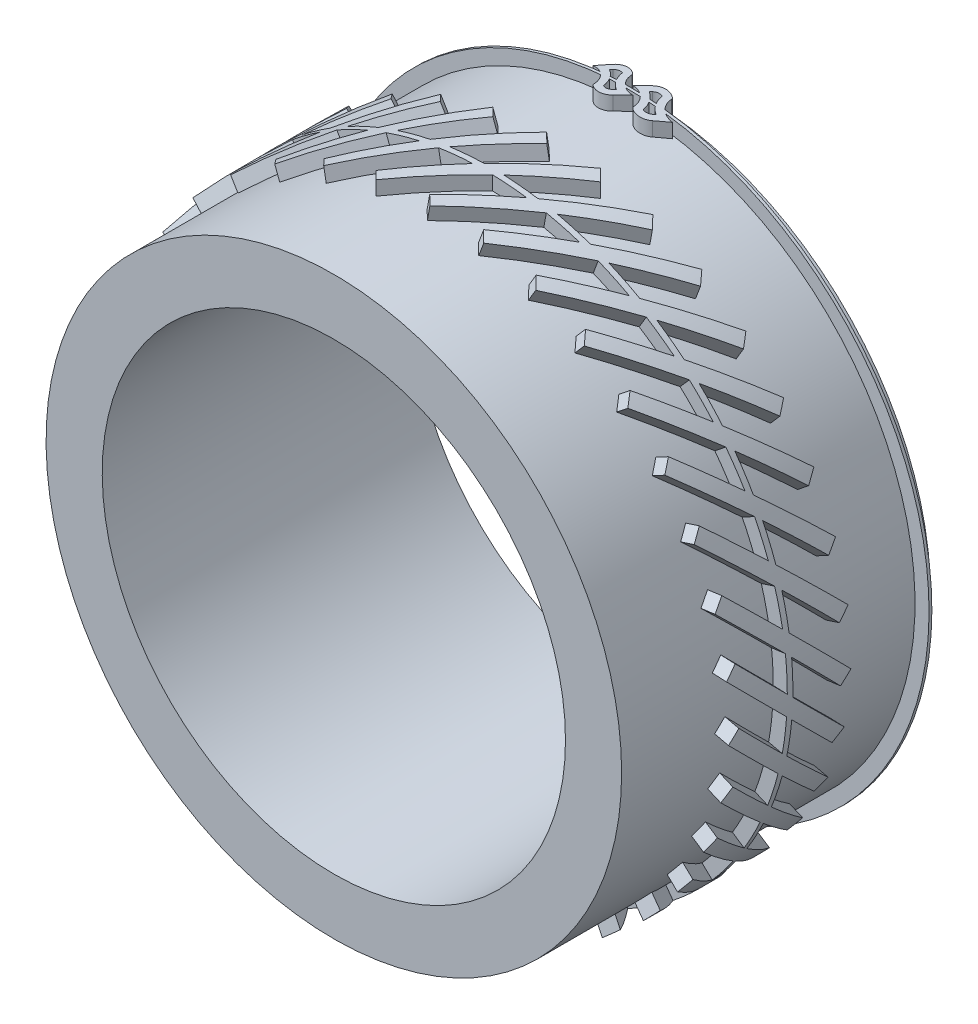
SolidWorks part; units mm, degrees
note: The reader was unsure of these and kept them because the rebuilt part matched: shared geometry of "Sketch1<4>", "Sketch1<5>", "Sketch4<9>".
ref_plane "Front Plane" through (0, 0, 0) normal (0, 0, 1) x (1, 0, 0)
ref_plane "Top Plane" through (0, 0, 0) normal (0, 1, 0) x (1, 0, 0)
ref_plane "Right Plane" through (0, 0, 0) normal (1, 0, 0) x (0, 0, -1)
sketch "Sketch1" plane through (0, 0, 0) normal (0, 0, 1) x (1, 0, 0)
  circle A0 centre (0, 0) radius 10.4775
  circle A1 centre (0, 0) radius 13.6525
  circle A2 centre (0, 0) radius 13.0175
  dimension "D1" = 20.955
  dimension "D2" = 3.175
  dimension "D3" = 2.54
ref_plane "Plane1" through (0, 0, 0) normal (1, 0, 0) x (0, 0, -1)
ref_plane "Plane2" through (0, 0, 0) normal (0, 1, 0) x (1, 0, 0)
extrude "Boss-Extrude1" add sketch "Sketch1" along normal mid plane 13.97 contours A2 A0
extrude "Boss-Extrude2" add sketch "Sketch1<4>" along normal mid plane 0.254 contours A1 A2
sketch "Sketch1<4>" plane through (0, 0, 0) normal (0, 0, 1) x (1, 0, 0) same geometry as "Sketch1"
sketch "Sketch4" plane through (0, 0, 0) normal (0, 1, 0) x (1, 0, 0)
  line L0 (2.54, 2.54) -> (-2.54, -2.54) construction
  line L1 (0, 6.985) -> (0, 5.715) construction
  line L2 (-0.3015, 5.9395) -> (-0.2253, 6.0158)
  line L3 (2.7645, 2.3155) -> (-2.3155, -2.7645)
  line L4 (2.3155, 2.7645) -> (-2.7645, -2.3155)
  line L5 (-2.7645, -2.3155) -> (-2.3155, -2.7645)
  line L6 (2.3155, 2.7645) -> (2.7645, 2.3155)
  line L7 (1.4945, 5.9395) -> (1.5708, 6.0158)
  line L8 (0, 6.536) -> (0, 5.715) construction
  line L10 (-0.077, 5.715) -> (0.833, 5.715)
  line L11 (-0.461, 6.985) -> (0.449, 6.985)
  line L12 (1.335, 6.985) -> (2.168, 6.985)
  line L13 (0.05, 5.842) -> (0.8111, 5.842)
  line L14 (-0.4391, 6.858) -> (0.322, 6.858)
  line L16 (-0.077, 5.842) -> (0.833, 5.842) construction
  line L17 (0.449, 6.985) -> (0, 6.536)
  line L18 (-0.461, 6.858) -> (0.449, 6.858) construction
  line L19 (-1.347, 6.985) -> (-1.796, 6.536)
  line L20 (-0.077, 5.715) -> (0.372, 6.164)
  line L21 (1.719, 5.715) -> (2.168, 6.164)
  line L22 (1.3569, 6.858) -> (2.168, 6.858)
  line L23 (-1.347, 6.985) -> (-1.796, 6.985)
  line L24 (-1.1225, 6.7605) -> (-1.1988, 6.6842)
  line L25 (-1.796, 5.842) -> (-1.796, 5.715)
  line L26 (-1.796, 6.858) -> (-1.474, 6.858)
  line L27 (-1.796, 5.715) -> (-0.963, 5.715)
  line L28 (-1.796, 5.842) -> (-0.9849, 5.842)
  line L29 (1.846, 5.842) -> (2.168, 5.842)
  line L30 (2.168, 5.842) -> (2.168, 5.715)
  line L31 (2.168, 5.715) -> (1.719, 5.715)
  line L32 (2.168, 6.985) -> (2.168, 6.858)
  line L33 (-1.796, 6.985) -> (-1.796, 6.858)
  line L34 (1.6292, 5.8048) -> (1.9001, 6.0757)
  line L35 (-0.1668, 5.8048) -> (0.104, 6.0757)
  line L36 (0.5388, 6.8952) -> (0.2679, 6.6243)
  line L37 (-1.2572, 6.8952) -> (-1.5281, 6.6243)
  line L38 (0.6735, 6.7605) -> (0.5973, 6.6842)
  arc A0 (1.719, 5.715) -> (0.8653, 5.6747) centre (1.27, 6.164) cw
  arc A1 (1.3027, 7.0253) -> (0.449, 6.985) centre (0.898, 6.536) ccw
  arc A2 (-0.9308, 5.6747) -> (-0.077, 5.715) centre (-0.526, 6.164) ccw
  arc A3 (-0.4933, 7.0253) -> (-1.347, 6.985) centre (-0.898, 6.536) ccw
  arc A4 (-1.796, 6.536) -> (-0.9766, 5.7648) centre (-1.796, 5.715) cw
  arc A5 (0, 6.536) -> (0.8195, 5.7648) centre (0, 5.715) cw
  arc A6 (-0.4475, 6.9352) -> (0.372, 6.164) centre (0.372, 6.985) ccw
  arc A7 (1.3486, 6.9352) -> (2.168, 6.164) centre (2.168, 6.985) ccw
  arc A8 (-0.4475, 6.9352) -> (-0.4933, 7.0253) centre (-0.5743, 6.9275) ccw
  arc A9 (-0.9766, 5.7648) -> (-0.9308, 5.6747) centre (-0.8498, 5.7726) ccw
  arc A10 (0.8195, 5.7648) -> (0.8653, 5.6747) centre (0.9462, 5.7726) ccw
  arc A11 (1.3486, 6.9352) -> (1.3027, 7.0253) centre (1.2218, 6.9274) ccw
  arc A12 (1.2218, 6.9274) -> (0.5388, 6.8952) centre (0.898, 6.536) ccw
  arc A13 (1.2218, 6.9274) -> (1.2218, 6.9274) centre (1.2218, 6.9274) ccw
  arc A14 (1.2218, 6.9274) -> (1.9001, 6.0757) centre (2.168, 6.985) ccw
  arc A15 (-0.5743, 6.9275) -> (-1.2572, 6.8952) centre (-0.898, 6.536) ccw
  arc A16 (-0.5743, 6.9275) -> (-0.5743, 6.9275) centre (-0.5743, 6.9275) ccw
  arc A17 (-0.5743, 6.9275) -> (0.104, 6.0757) centre (0.372, 6.985) ccw
  arc A18 (0.2679, 6.6243) -> (0.9462, 5.7726) centre (0, 5.715) cw
  arc A19 (0.9462, 5.7726) -> (0.9462, 5.7726) centre (0.9462, 5.7726) ccw
  arc A20 (1.6292, 5.8048) -> (0.9462, 5.7726) centre (1.27, 6.164) cw
  arc A21 (-1.5281, 6.6243) -> (-0.8498, 5.7726) centre (-1.796, 5.715) cw
  arc A22 (-0.8498, 5.7726) -> (-0.8498, 5.7726) centre (-0.8498, 5.7726) ccw
  arc A23 (-0.8498, 5.7726) -> (-0.1668, 5.8048) centre (-0.526, 6.164) ccw
  arc A24 (-0.7544, 6.8191) -> (-1.1225, 6.7605) centre (-0.898, 6.536) ccw
  arc A25 (-0.7544, 6.8191) -> (-0.7544, 6.8191) centre (-0.7544, 6.8191) ccw
  arc A26 (-0.7544, 6.8191) -> (-0.2253, 6.0158) centre (0.372, 6.985) ccw
  arc A27 (1.0417, 6.8191) -> (0.6735, 6.7605) centre (0.898, 6.536) ccw
  arc A28 (1.0417, 6.8191) -> (1.0417, 6.8191) centre (1.0417, 6.8191) ccw
  arc A29 (1.0417, 6.8191) -> (1.5708, 6.0158) centre (2.168, 6.985) ccw
  arc A30 (-1.1988, 6.6842) -> (-0.6697, 5.8809) centre (-1.796, 5.715) cw
  arc A31 (-0.6697, 5.8809) -> (-0.6697, 5.8809) centre (-0.6697, 5.8809) ccw
  arc A32 (-0.6697, 5.8809) -> (-0.3015, 5.9395) centre (-0.526, 6.164) ccw
  arc A33 (0.5973, 6.6842) -> (1.1263, 5.8809) centre (0, 5.715) cw
  arc A34 (1.1263, 5.8809) -> (1.1263, 5.8809) centre (1.1263, 5.8809) ccw
  arc A35 (1.4945, 5.9395) -> (1.1263, 5.8809) centre (1.27, 6.164) cw
  point P2 (0, 0)
  point P32 (10.2756, 5.9395)
  dimension "D4" = 0.635
  dimension "D3" = 0.127
  dimension "D1" = 0.3175
  dimension "D7" = 0.127
  dimension "D5" = 0.821
  dimension "D2" = 0.3175
  dimension "D6" = 0.127
  dimension "D8" = 0.127
  dimension "D9" = 0.127
  dimension "D10" = 0.1905
  dimension "D11" = 0.1905
extrude "Boss-Extrude3" add sketch "Sketch4" along normal up to surface (13.4547 mm away) contours L6 L3 L5 L4
pattern_circular "CirPattern1" count 35 over 360 about axis through (0, 0, 0) along (0, 0, 1) of "Boss-Extrude3"
extrude "Cut-Extrude2" cut sketch "Sketch1<5>" against normal mid plane 13.97 contours A0
sketch "Sketch1<5>" plane through (0, 0, 0) normal (0, 0, 1) x (1, 0, 0) same geometry as "Sketch1"
extrude "Boss-Extrude4" add sketch "Sketch4<9>" along normal up to surface (13.5859 mm away) contours A4 A9 A2 L20 A6 A8 A3 L19 A23 A21 L37 A15 A17 L35 | A7 A11 A1 L17 A5 A10 A0 L21 L34 A20 A18 L36 A12 A14 | A21 A23 L35 A17 A15 L37 A32 A30 L24 A24 A26 L2 | A20 L34 A14 A12 L36 A18 L7 A35 A33 L38 A27 A29 | L27 L25 L28
sketch "Sketch4<9>" plane through (0, 0, 0) normal (0, 1, 0) x (1, 0, 0) same geometry as "Sketch4"
ref_plane "Plane3" through (0, 0, -6.35) normal (0, 0, -1) x (-1, 0, 0)
sketch "Sketch6" plane through (0, 0, -6.35) normal (0, 0, -1) x (-1, 0, 0)
  circle A0 centre (0, 0) radius 10.4775
  circle A1 centre (0, 0) radius 13.6525
extrude "Boss-Extrude6" add sketch "Sketch6" along normal mid plane 0.127
